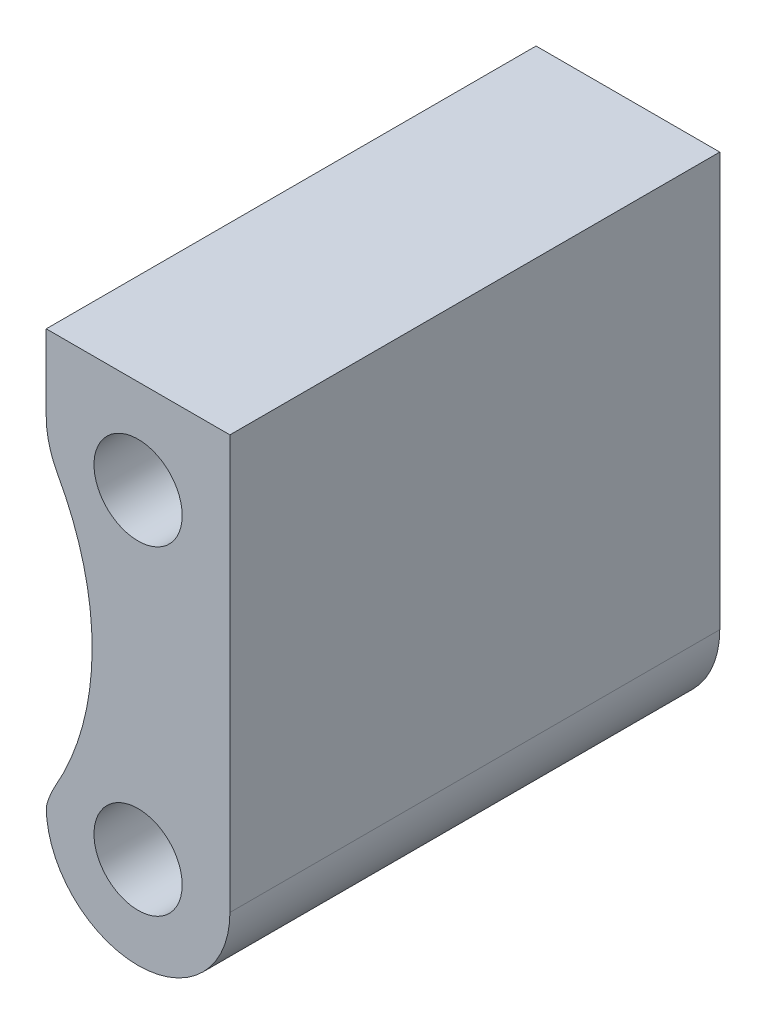
SolidWorks part; units mm, degrees
ref_plane "Front Plane" through (0, 0, 0) normal (0, 0, 1) x (1, 0, 0)
ref_plane "Top Plane" through (0, 0, 0) normal (0, 1, 0) x (1, 0, 0)
ref_plane "Right Plane" through (0, 0, 0) normal (1, 0, 0) x (0, 0, -1)
sketch "Sketch1" plane through (0, 0, 0) normal (0, 0, 1) x (1, 0, 0)
  line L0 (0, 16.5862) -> (0, 0) construction
  line L1 (0, 16.5862) -> (0, 0) construction
  line L2 (4.7625, 16.5862) -> (4.7625, 0)
  line L3 (-4.7625, 16.5862) -> (-4.7625, 0)
  line L4 (-4.7625, 16.5862) -> (-4.7625, 21.4478)
  line L5 (-4.7625, 21.4478) -> (4.7625, 21.4478)
  line L6 (4.7625, 21.4478) -> (4.7625, 16.5862)
  circle A0 centre (0, 0) radius 2.286
  circle A1 centre (0, 16.5862) radius 2.286
  arc A3 (-4.7625, 0) -> (4.7625, 0) centre (0, 0) ccw
  dimension "D1" = 4.572
  dimension "D3" = 4.7625
  dimension "D2" = 16.5862
  dimension "D4" = 4.8616
extrude "Boss-Extrude1" add sketch "Sketch1" along normal blind 25.4
sketch "Sketch2" plane through (0, 0, 25.4) normal (0, 0, 1) x (1, 0, 0)
  line L1 (0, 16.5862) -> (0, 0) construction
  circle A0 centre (-16.67, 8.2931) radius 14.2875
  point P4 (0, 0)
  point P7 (0, 8.2931)
  dimension "D2" = 28.575
  dimension "D1" = 16.67
extrude "Cut-Extrude1" cut sketch "Sketch2" against normal through all
fillet "Fillet1" radius 4.7625 2 edges at (-4.7625, 0.3973, 12.7) (-4.7625, 16.1889, 12.7)
